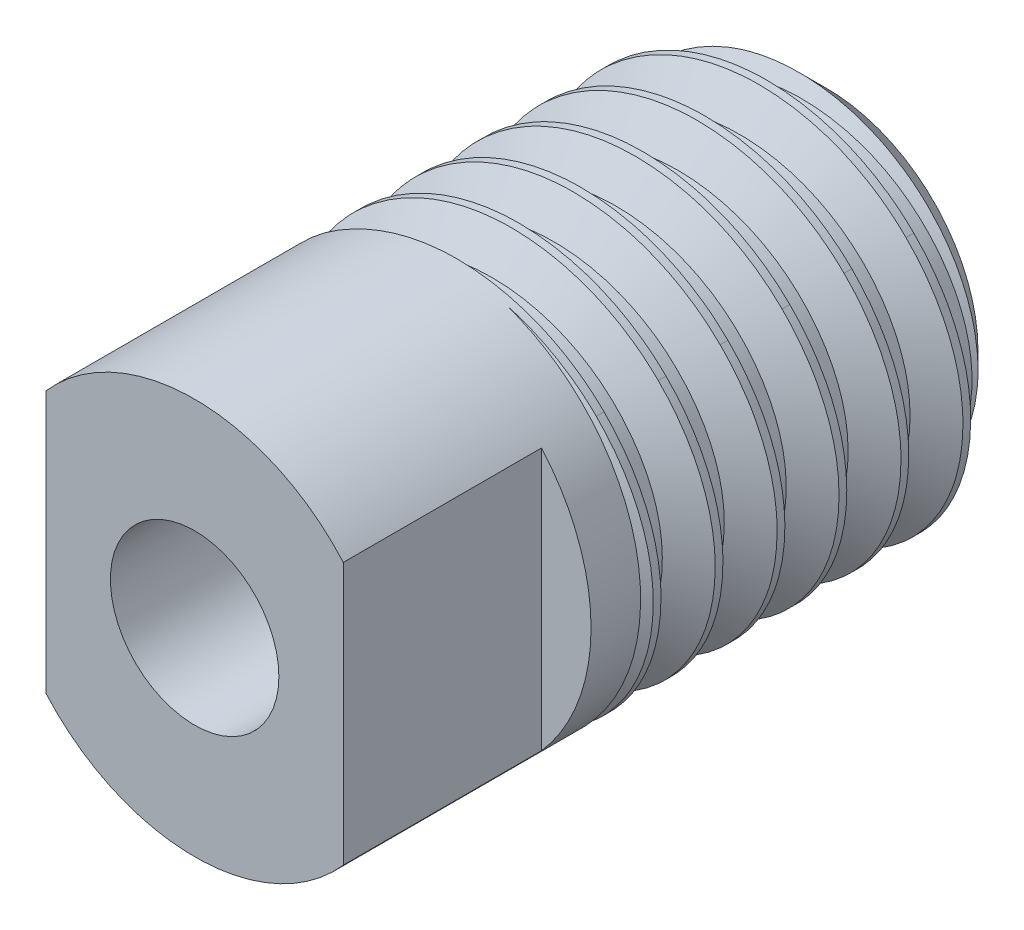
SolidWorks part; units mm, degrees
material "Plain Carbon Steel"
ref_plane "Front Plane" through (0, 0, 0) normal (0, 0, 1) x (1, 0, 0)
ref_plane "Top Plane" through (0, 0, 0) normal (0, 1, 0) x (1, 0, 0)
ref_plane "Right Plane" through (0, 0, 0) normal (1, 0, 0) x (0, 0, -1)
sketch "Sketch3" plane through (0, 0, 0) normal (1, 0, 0) x (0, 0, -1)
  line L0 (-36.6761, 0) -> (47.8563, 0) construction
  line L1 (0, 1.7) -> (0, 4)
  line L2 (0, 4) -> (7.75, 4)
  line L3 (7.75, 4) -> (7.75, 2.825)
  line L4 (0, 1.7) -> (0.75, 1.7)
  line L5 (0.75, 1.7) -> (0.75, 2.825)
  line L6 (0.75, 2.825) -> (7.75, 2.825)
  dimension "D1" = 1.7
  dimension "D2" = 7
  dimension "D3" = 4
  dimension "D4" = 2.825
  dimension "D5" = 0.75
revolve "Revolve1" add sketch "Sketch3" angle 360 about L0
thread "Thread1" pitch 1.25 method cut trim with start face yes trim with end face yes profile "Thread Profile1" start angle 0, offset 1.25, length 10, pitch 1.25, diameter 8
ref_plane "Plane1" through (4, 0, -9) normal (0, -1, 0) x (1, 0, 0)
sketch "Thread Profile1" plane through (4, 0, -9) normal (0, -1, 0) x (1, 0, 0)
  line L0 (0, 0) -> (0, 1.25) construction
  line L11 (0, 0) -> (0, 1.0937)
  line L12 (0, 1.0937) -> (-0.6766, 0.7031)
  line L13 (-0.6766, 0.7031) -> (-0.6766, 0.3906)
  line L15 (-0.6766, 0.3906) -> (0, 0)
  line L17 (-0.6766, 0.5469) -> (0, 0.5469) construction
  point P2 (0, 0)
  dimension "Pitch" = 1.25
  dimension "Profile_Angle" = 60
  dimension "Profile_Land" = 0.3125
  dimension "Profile_Height" = 0.6766
sketch "Sketch9" plane through (0, 0, 0) normal (0, 0, 1) x (1, 0, 0)
  circle A0 centre (0, 0) radius 4
  circle A1 centre (0, 0) radius 4 construction
  circle A2 centre (0, 0) radius 1.7
  circle A3 centre (0, 0) radius 1.7 construction
extrude "Boss-Extrude1" add sketch "Sketch9" along normal blind 1
sketch "Sketch10" plane through (0, 0, 1) normal (0, 0, 1) x (1, 0, 0)
  line L2 (-3, -2.6458) -> (-3, 2.6458)
  line L4 (3, -2.6458) -> (3, 2.6458)
  line L6 (-3, 2.6458) -> (3, -2.6458) construction
  circle A0 centre (0, 0) radius 4 construction
  arc A1 (-3, -2.6458) -> (3, -2.6458) centre (0, 0) ccw
  arc A2 (3, 2.6458) -> (-3, 2.6458) centre (0, 0) ccw
  circle A3 centre (0, 0) radius 1.7
  circle A4 centre (0, 0) radius 1.7 construction
  circle A5 centre (0, 0) radius 1.7
  circle M9 centre (0, 0) radius 4
  circle M10 centre (0, 0) radius 1.7
  dimension "D1" = 8
  dimension "D2" = 6
extrude "Boss-Extrude2" add sketch "Sketch10" along normal blind 4 contours L6 L2 M9 M10 | L6 A5 L4 M9 region at (-0.8079, -1.7413, 1) region at (0.8079, 1.7413, 1)
sketch "Sketch11" plane through (0, 0, 0) normal (1, 0, 0) x (0, 0, -1)
  line L0 (6.8089, 4) -> (8.0733, 2.7356)
  line L1 (6.8089, 4) -> (1.1875, 4) construction
  line L2 (6.8089, 4) -> (6.8089, 4.4654)
  line L3 (6.8089, 4.4654) -> (8.0733, 4.4654)
  line L4 (8.0733, 4.4654) -> (8.0733, 2.7356)
  line L5 (-5.889, 0) -> (8.801, 0) construction
  dimension "D1" = 45
revolve "Cut-Revolve1" cut sketch "Sketch11" angle 360 about L5
